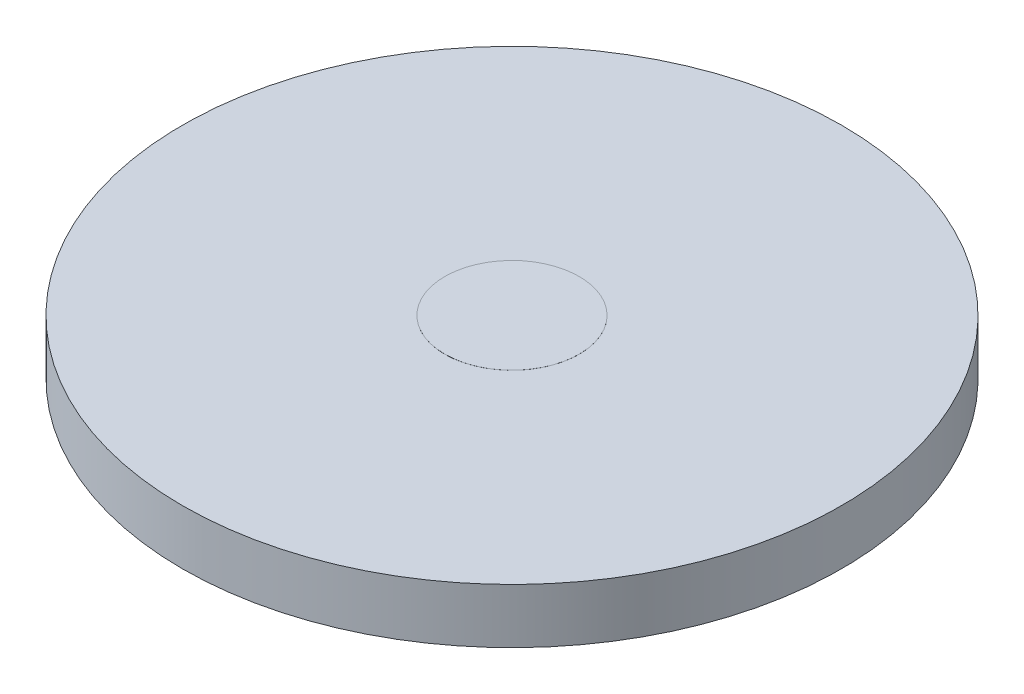
SolidWorks part; units mm, degrees
note: '?' marks a value the reader was unsure of.
material "Fiberglass Desiccant"
ref_plane "Front Plane" through (0, 0, 0) normal (0, 0, 1) x (1, 0, 0)
ref_plane "Top Plane" through (0, 0, 0) normal (0, 1, 0) x (1, 0, 0)
ref_plane "Right Plane" through (0, 0, 0) normal (1, 0, 0) x (0, 0, -1)
sketch "Sketch1" plane through (0, 0, 0) normal (0, 1, 0) x (1, 0, 0)
  circle A0 centre (0, 0) radius 121.5
  dimension "D1" = 243
extrude "Boss-Extrude1" add sketch "Sketch1" along normal mid plane 20.18 contours A0
sketch "Sketch2" plane through (0, 0, 0) normal (0, 1, 0) x (1, 0, 0)
  circle A0 centre (0, 0) radius 24.795
  dimension "D1" = 49.59
extrude "Boss-Extrude2" add sketch "Sketch2" along normal offset from surface 0.02 and the other way offset from surface (10.39 mm away) 0.3 up to face at (0, 10.09, 121.5) offset beyond the face yes other way up to face at (0, -10.09, 121.5)
ref_axis "Axis1" through (0, 16.521, 0) along (0, -1, 0)?
